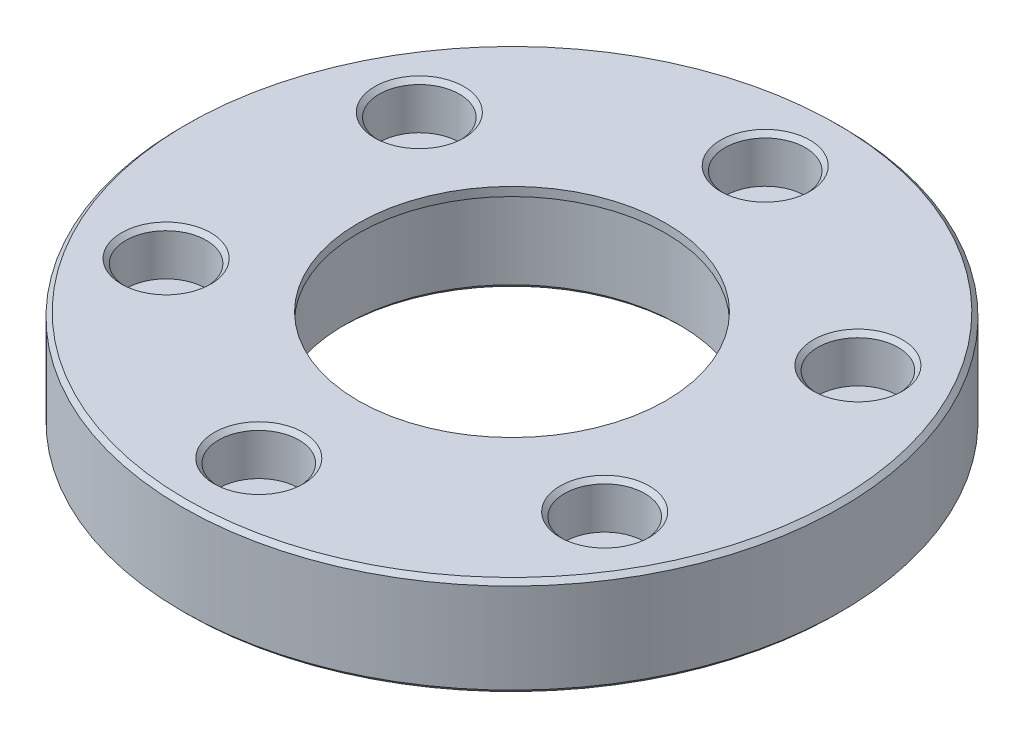
SolidWorks part; units mm, degrees
ref_plane "前视基准面" through (0, 0, 0) normal (0, 0, 1) x (1, 0, 0)
ref_plane "上视基准面" through (0, 0, 0) normal (0, 1, 0) x (1, 0, 0)
ref_plane "右视基准面" through (0, 0, 0) normal (1, 0, 0) x (0, 0, -1)
other "Configuration Table"
sketch "草图1" plane through (0, 0, 0) normal (0, 1, 0) x (1, 0, 0)
  circle A0 centre (0, 0) radius 7
  circle A1 centre (0, 0) radius 15
  circle A2 centre (0, 0) radius 11.525 construction
  circle A3 centre (0, 11.525) radius 1.83
  circle A4 centre (9.9809, 5.7625) radius 1.83
  circle A5 centre (9.9809, -5.7625) radius 1.83
  circle A6 centre (0, -11.525) radius 1.83
  circle A7 centre (-9.9809, -5.7625) radius 1.83
  circle A8 centre (-9.9809, 5.7625) radius 1.83
  point P19 (0, 0)
  dimension "D1" = 14
  dimension "D2" = 30
  dimension "D3" = 23.05
  dimension "D4" = 3.66
  dimension "D5" = 6
extrude "凸台-拉伸1" add sketch "草图1" along normal blind 2.1
sketch "草图2" plane through (0, 0, 0) normal (0, -1, 0) x (-1, 0, 0)
  circle A0 centre (0, 0) radius 7 construction
  circle A1 centre (0, 0) radius 15 construction
  circle A2 centre (0, 0) radius 7
  circle A3 centre (0, 0) radius 15
  circle A4 centre (0, 11.53) radius 0.9
  circle A6 centre (0, 0) radius 11.53 construction
  circle A7 centre (9.9853, 5.765) radius 0.9
  circle A8 centre (9.9853, -5.765) radius 0.9
  circle A9 centre (0, -11.53) radius 0.9
  circle A10 centre (-9.9853, -5.765) radius 0.9
  circle A11 centre (-9.9853, 5.765) radius 0.9
  point P21 (0, 0)
  dimension "D1" = 1.8
  dimension "D2" = 23.06
  dimension "D3" = 6
extrude "凸台-拉伸2" add sketch "草图2" along normal blind 2.4
sketch "草图3" plane through (0, -2.4, 0) normal (0, -1, 0) x (-1, 0, 0)
  circle A0 centre (0, 0) radius 7.6
  dimension "D1" = 15.2
extrude "切除-拉伸1" cut sketch "草图3" against normal blind 4.1
chamfer "倒角1" distance 0.2 angle 45 15 edges at (0, -2.4, -15) (-9.9809, 2.1, -3.9325) (0, 2.1, 13.355) (9.9809, 2.1, -3.9325) (0, 2.1, 15) (0, 2.1, -9.695) (9.9809, 2.1, 7.5925) (-9.9809, 2.1, 7.5925) (9.9853, -2.4, -6.665) (0, -2.4, 10.63) (-9.9853, -2.4, -6.665) (0, -2.4, -12.43) (-9.9853, -2.4, 4.865) (9.9853, -2.4, 4.865) (0, -2.4, -7.6)
chamfer "倒角2" distance 0.3 angle 45 1 edges at (0, 1.7, -7.6)
